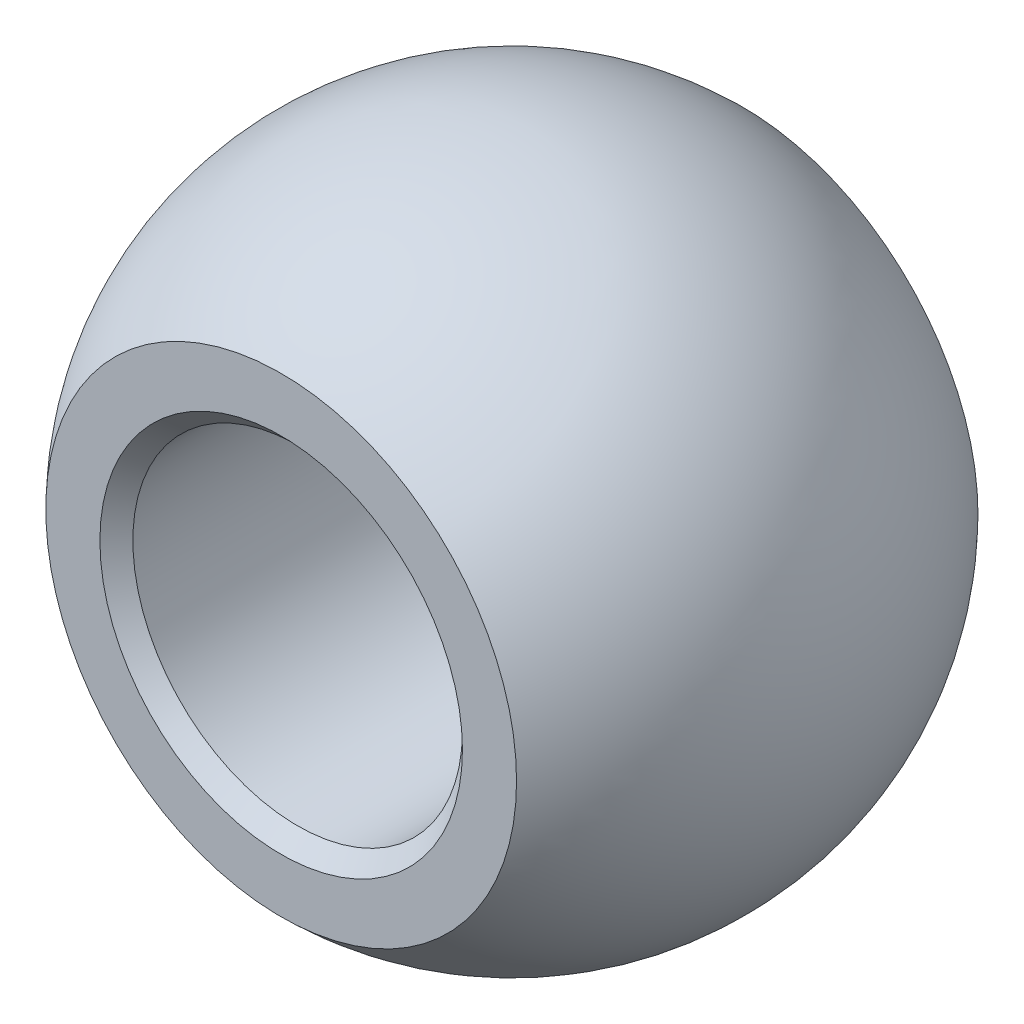
SolidWorks part; units mm, degrees
material "Plain Carbon Steel"
ref_plane "Front" through (0, 0, 0) normal (0, 0, 1) x (1, 0, 0)
ref_plane "Top" through (0, 0, 0) normal (0, 1, 0) x (1, 0, 0)
ref_plane "Right" through (0, 0, 0) normal (1, 0, 0) x (0, 0, -1)
sketch "Sketch1" plane through (0, 0, 0) normal (0, 0, 1) x (1, 0, 0)
  line L0 (0, 0) -> (0, -31.75)
  line L1 (0, -31.75) -> (3.9751, -31.75)
  line L2 (3.9751, -31.75) -> (3.9751, 0)
  line L3 (3.9751, 0) -> (0, 0)
  line L5 (0, 26.9875) -> (0, 0) construction
  line L6 (0, 26.9875) -> (11.1125, 26.9875) construction
  line L7 (11.1125, 26.9875) -> (11.1125, 15.875) construction
  line L8 (-3.9751, -31.75) -> (-3.9751, 0) construction
  line L9 (4.0898, -31.6838) -> (4.0898, -32.743)
  line L10 (4.0898, -32.743) -> (3.1725, -32.2134)
  line L11 (3.2871, -32.2796) -> (3.2871, -32.1472)
  line L12 (3.1725, -32.2134) -> (4.0898, -31.6838)
  line L13 (4.0324, -31.7169) -> (4.0324, -32.7099)
  line L14 (4.0898, -32.2134) -> (3.9751, -32.2134)
  line L15 (3.9751, -31.75) -> (3.9751, -32.6768)
  line L16 (3.1725, -32.2134) -> (3.2871, -32.2134)
  arc A0 (7.3754, 7.5629) -> (0, 26.9875) centre (0, 15.875) ccw construction
  circle A1 centre (0, 15.875) radius 3.9688 construction
  circle A2 centre (0, 15.875) radius 7.9375 construction
  circle A3 centre (0, 15.875) radius 8.0169 construction
  arc A4 (3.9751, 0) -> (7.3754, 7.5629) centre (14.0859, 0) cw construction
  point P24 (0, 23.8125)
  point P26 (3.9751, -32.2134)
  point P28 (4.0324, -32.2134)
  dimension "A" = 7.9375
  dimension "Ball Dia" = 15.875
  dimension "B" = 22.225
  dimension "D1" = 16.0337
  dimension "D" = 47.625
  dimension "E" = 31.75
  dimension "Thread Dia" = 7.9502
  dimension "D2" = 60
  dimension "Pitch" = 1.0592
  dimension "D4" = 0.1324
sketch "Sketch2" plane through (0, 0, 0) normal (1, 0, 0) x (0, 0, -1)
  line L0 (3.9688, 15.875) -> (-3.9687, 15.875)
  line L1 (3.9688, 16.6464) -> (0, 15.875) construction
  line L2 (3.9688, 15.1036) -> (0, 15.875) construction
  line L6 (5.5563, 15.875) -> (-5.5562, 15.875)
  line L7 (0, 11.9063) -> (0, 19.8438)
  line L8 (0, 26.9875) -> (0, 0) construction
  line L9 (0, 19.8438) -> (0, 11.9063) construction
  circle A0 centre (0, 15.875) radius 7.9375
  circle A1 centre (0, 15.875) radius 11.1125
  point P4 (0, 15.875)
  point P7 (0, 23.8125)
  point P9 (0, 7.9375)
  point P14 (0, 15.875)
  point P18 (0, 15.875)
  point P23 (11.1125, 15.875)
  point P25 (-11.1125, 15.875)
  dimension "OAWidth" = 7.9375
  dimension "Swivel" = 22
  dimension "BallWidth" = 11.1125
sketch "Sketch15" plane through (0, 0, 0) normal (0, 0, 1) x (1, 0, 0)
  line L0 (0, 26.9875) -> (0, 0) construction
  line L1 (11.1125, 26.9875) -> (-11.1125, 26.9875)
  line L2 (11.1125, 26.9875) -> (11.1125, 0)
  line L3 (11.1125, 0) -> (-11.1125, 0)
  line L4 (-11.1125, 26.9875) -> (-11.1125, 0)
  line L5 (3.9751, 0) -> (0, 0) construction
  point P5 (0, 26.9875)
sketch "Sketch14" plane through (0, 0, 0) normal (0, 0, 1) x (1, 0, 0)
  line L1 (0, 0) -> (0, -31.75) construction
  line L2 (0, -31.75) -> (3.9751, -31.75) construction
  line L3 (3.9751, -31.75) -> (3.9751, 0) construction
  line L5 (0, 0) -> (0, -31.75)
  line L6 (0, -31.75) -> (3.9751, -31.75)
  line L7 (3.9751, -31.75) -> (3.9751, 0)
  line L8 (3.9751, 0) -> (0, 0) construction
  line L9 (3.9751, 0) -> (0, 0)
revolve "Revolve4" add sketch "Sketch14" angle 360 about L0
sketch "Sketch21" plane through (0, 0, 0) normal (0, 0, 1) x (1, 0, 0)
  line L0 (0, 26.9875) -> (0, 0) construction
  line L1 (3.9751, 0) -> (0, 0) construction
  line L2 (0, 26.9875) -> (0, 0)
  line L3 (3.9751, 0) -> (0, 0)
  arc A0 (7.3754, 7.5629) -> (3.9751, 0) centre (14.0859, 0) ccw construction
  arc A1 (7.3754, 7.5629) -> (0, 26.9875) centre (0, 15.875) ccw construction
  arc A2 (7.3754, 7.5629) -> (3.9751, 0) centre (14.0859, 0) ccw
  arc A3 (7.3754, 7.5629) -> (0, 26.9875) centre (0, 15.875) ccw
revolve "Revolve5" add sketch "Sketch21" angle 360 about L0
sketch "Sketch24" plane through (0, 0, 0) normal (1, 0, 0) x (0, 0, -1)
  line L0 (3.9688, 15.875) -> (3.9688, 26.9875)
  line L1 (3.9688, 26.9875) -> (11.1125, 26.9875)
  line L2 (11.1125, 0) -> (11.1125, 26.9875)
  line L3 (3.9688, 15.875) -> (3.9688, 0.7937)
  line L4 (3.9688, 0.7937) -> (3.9751, 0)
  line L5 (3.9751, 0) -> (11.1125, 0)
  line L6 (0, 26.9875) -> (0, 0) construction
  line L7 (0, 26.9875) -> (0, 0) construction
  line L8 (-3.9751, 0) -> (-11.1125, 0)
  line L9 (-3.9687, 0.7937) -> (-3.9751, 0)
  line L10 (-3.9687, 15.875) -> (-3.9687, 0.7937)
  line L11 (-11.1125, 0) -> (-11.1125, 26.9875)
  line L12 (-3.9688, 26.9875) -> (-11.1125, 26.9875)
  line L13 (-3.9687, 15.875) -> (-3.9688, 26.9875)
  dimension "D1" = 0.7937
extrude "Cut-Extrude10" cut sketch "Sketch24" against normal through all both and the other way through all
sketch "Sketch17" plane through (0, 0, 0) normal (0, 0, 1) x (1, 0, 0)
  circle A2 centre (0, 15.875) radius 8.0169 construction
  circle A3 centre (0, 15.875) radius 8.0169
extrude "Cut-Extrude9" cut sketch "Sketch17" against normal through all both and the other way through all
sketch "Sketch7" plane through (0, 0, 0) normal (0, 0, 1) x (1, 0, 0)
  line L0 (0, 23.8125) -> (0, 7.9375)
  line L1 (0, 26.9875) -> (0, 0) construction
  line L2 (0, 0) -> (0, 7.9375) construction
  arc A0 (0, 7.9375) -> (0, 23.8125) centre (0, 15.875) ccw
  circle A1 centre (0, 15.875) radius 7.9375 construction
revolve "Revolve3" add sketch "Sketch7" angle 360 about L2
sketch "Sketch10" plane through (0, 0, 0) normal (0, 0, 1) x (1, 0, 0)
  circle A0 centre (0, 15.875) radius 3.9688 construction
  circle A1 centre (0, 15.875) radius 3.9688
extrude "Cut-Extrude4" cut sketch "Sketch10" against normal through all and the other way through all
sketch "Sketch22" plane through (0, 0, 0) normal (0, 0, 1) x (1, 0, 0)
  line L0 (-11.1125, 26.9875) -> (-11.1125, 0) construction
  line L1 (11.1125, 0) -> (-11.1125, 0) construction
  line L2 (11.1125, 26.9875) -> (11.1125, 0) construction
  line L3 (11.1125, 26.9875) -> (-11.1125, 26.9875) construction
  line L4 (-11.1125, 26.9875) -> (-11.1125, 0)
  line L5 (11.1125, 0) -> (-11.1125, 0)
  line L6 (11.1125, 26.9875) -> (11.1125, 0)
  line L7 (11.1125, 26.9875) -> (-11.1125, 26.9875)
extrude "Cut-Extrude7" cut sketch "Sketch22" against normal through all from vertex starting at point (0, 15.875, -5.5563)
sketch "Sketch23" plane through (0, 0, 0) normal (0, 0, 1) x (1, 0, 0)
  line L0 (-11.1125, 26.9875) -> (-11.1125, 0) construction
  line L1 (11.1125, 0) -> (-11.1125, 0) construction
  line L2 (11.1125, 26.9875) -> (11.1125, 0) construction
  line L3 (11.1125, 26.9875) -> (-11.1125, 26.9875) construction
  line L4 (-11.1125, 26.9875) -> (-11.1125, 0)
  line L5 (11.1125, 0) -> (-11.1125, 0)
  line L6 (11.1125, 26.9875) -> (11.1125, 0)
  line L7 (11.1125, 26.9875) -> (-11.1125, 26.9875)
extrude "Cut-Extrude8" cut sketch "Sketch23" along normal through all from vertex starting at point (0, 15.875, 5.5562)
chamfer "Chamfer1" distance 1.0592 angle 45 1 edges at (-3.9751, -31.75, 0)
chamfer "Chamfer2" distance 0.3969 angle 45 2 edges at (3.9688, 15.875, 5.5562) (3.9688, 15.875, -5.5563)
sketch "Sketch18" [suppressed] plane through (0, -31.75, 0) normal (0, -1, 0) x (1, 0, 0)
  circle A0 centre (0, 0) radius 3.9751 construction
  circle A1 centre (0, 0) radius 3.9751
curve "Helix/Spiral1" [suppressed] pitch 1.0592 height 32.8092 turns 30.976
sketch "Sketch19" [suppressed] plane through (0, 0, 0) normal (0, 0, 1) x (1, 0, 0)
  line L0 (3.2871, -32.2796) -> (3.2871, -32.1472) construction
  line L1 (3.1725, -32.2134) -> (4.0898, -31.6838) construction
  line L2 (4.0898, -32.743) -> (3.1725, -32.2134) construction
  line L3 (4.0324, -31.7169) -> (4.0324, -32.7099) construction
  line L4 (3.2871, -32.2796) -> (3.2871, -32.1472)
  line L5 (3.2871, -32.1472) -> (4.0324, -31.7169)
  line L6 (4.0324, -32.7099) -> (3.2871, -32.2796)
  line L7 (4.0324, -31.7169) -> (4.0324, -32.7099)
sweep "Cut-Sweep1" [suppressed] cut profiles "Sketch19" path "Helix/Spiral1"
ref_plane "Plane1" [suppressed] through (0, 0, 0) normal (0, 1, 0) x (1, 0, 0)
sketch "Sketch20" [suppressed] plane through (0, 0, 0) normal (0, 1, 0) x (1, 0, 0)
  circle A0 centre (0, 0) radius 3.9751
extrude "Boss-Extrude2" [suppressed] add sketch "Sketch20" against normal through all draft 60
combine bodies "Combine1" [suppressed] operation type add bodies to combine 130 133
delete or keep bodies "Body-Delete/Keep 1" type delete bodies bodies 122 133
equation "\"D1@Sketch1\"=\"Ball Dia@Sketch1\"*1.01"
equation "\"D1\"= \"A@Sketch1\" / 20"
equation "\"D3\"= \"E@Sketch1\" + .2"
equation "\"D4@Sketch1\"=\"Pitch@Sketch1\"/8"
equation "\"D1@Chamfer1\"=\"Pitch@Sketch1\""
equation "\"D4@Helix/Spiral1\"=\"Pitch@Sketch1\""
equation "\"D3@Helix/Spiral1\"=\"E@Sketch1\"+\"Pitch@Sketch1\""
equation "\"D1@Chamfer2\"=\"A@Sketch1\"/20"
equation "\"D1@Sketch24\"=(\"OAWidth@Sketch2\"/2)/5"
